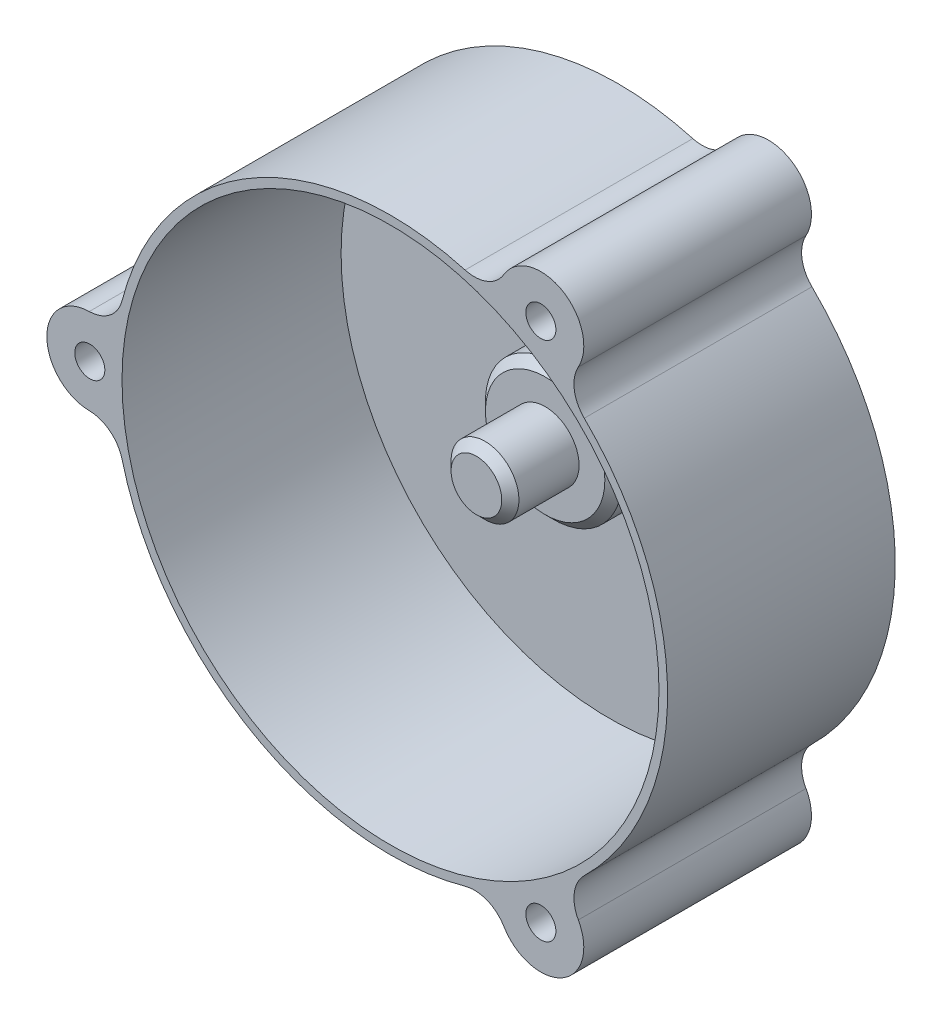
SolidWorks part; units mm, degrees
ref_plane "Front" through (0, 0, 0) normal (0, 0, 1) x (1, 0, 0)
ref_plane "Top" through (0, 0, 0) normal (0, 1, 0) x (1, 0, 0)
ref_plane "Right" through (0, 0, 0) normal (1, 0, 0) x (0, 0, -1)
sketch "Esquisse1" plane through (0, 0, 0) normal (0, 0, 1) x (1, 0, 0)
  circle A0 centre (0, 0) radius 31.25
  dimension "D1" = 62.5
extrude "Boss.-Extru.1" add sketch "Esquisse1" along normal blind 1
sketch "Esquisse2" plane through (0, 0, 1) normal (0, 0, 1) x (1, 0, 0)
  circle A0 centre (0, 0) radius 32.25
  circle A1 centre (0, 0) radius 31.25 construction
  circle A2 centre (0, 0) radius 31.25
  dimension "D1" = 1
extrude "Boss.-Extru.2" add sketch "Esquisse2" along normal blind 25.5 and the other way up to surface (1 mm away) other way up to face at (31.25, 0, 0)
sketch "Esquisse3" plane through (0, 0, 1) normal (0, 0, 1) x (1, 0, 0)
  circle A0 centre (0, 0) radius 7.95
  dimension "D1" = 15.9
extrude "Boss.-Extru.3" add sketch "Esquisse3" along normal blind 7.5
sketch "Esquisse4" plane through (0, 0, 8.5) normal (0, 0, 1) x (1, 0, 0)
  circle A0 centre (0, 0) radius 3.95
  dimension "D1" = 7.9
extrude "Boss.-Extru.4" add sketch "Esquisse4" along normal blind 8
chamfer "Chanfrein1" distance 1 angle 45 2 edges at (7.95, 0, 8.5) (3.95, 0, 16.5)
sketch "Esquisse5" plane through (0, 0, 26.5) normal (0, 0, 1) x (1, 0, 0)
  line L0 (-35, 0) -> (0, 0) construction
  arc A0 (-32.0009, -4.0007) -> (-32.0009, 4.0007) centre (-35, 0) cw
  circle A1 centre (0, 0) radius 32.25 construction
  arc A2 (-32.0009, 4.0007) -> (-32.0009, -4.0007) centre (0, 0) ccw
  dimension "D1" = 5
  dimension "D2" = 35
extrude "Boss.-Extru.5" add sketch "Esquisse5" against normal up to surface (26.5 mm away) up to face at (32.25, 0, 0)
sketch "Esquisse6" plane through (0, 0, 26.5) normal (0, 0, 1) x (1, 0, 0)
  circle A0 centre (-35, 0) radius 1.75
  dimension "D1" = 3.5
extrude "Enlèv. mat.-Extru.1" cut sketch "Esquisse6" against normal blind 10
fillet "Congé1" radius 4 2 edges at (-32.0009, 4.0007, 13.25) (-32.0009, -4.0007, 13.25)
pattern_circular "Répétition circulaire2" count 3 over 360 about axis through (0, 0, 26.5) along (0, 0, 1) of "Boss.-Extru.5", "Enlèv. mat.-Extru.1", "Congé1"
sketch "Esquisse7" plane through (0, 0, 26.5) normal (0, 0, 1) x (1, 0, 0)
  arc A12 (-35.064, 4.9996) -> (-35.064, -4.9996) centre (-35, 0) ccw
  arc A13 (-31.2404, -8.0062) -> (-35.064, -4.9996) centre (-35.1152, -8.9993) ccw
  arc A14 (-31.2404, -8.0062) -> (8.6866, -31.0581) centre (0, 0) ccw
  arc A15 (13.2022, -32.8661) -> (8.6866, -31.0581) centre (9.764, -34.9103) ccw
  arc A16 (13.2022, -32.8661) -> (21.8618, -27.8665) centre (17.5, -30.3109) ccw
  arc A17 (22.5538, -23.0519) -> (21.8618, -27.8665) centre (25.3512, -25.911) ccw
  arc A18 (22.5538, -23.0519) -> (22.5538, 23.0519) centre (0, 0) ccw
  arc A19 (21.8618, 27.8665) -> (22.5538, 23.0519) centre (25.3512, 25.911) ccw
  arc A20 (21.8618, 27.8665) -> (13.2022, 32.8661) centre (17.5, 30.3109) ccw
  arc A21 (8.6866, 31.0581) -> (13.2022, 32.8661) centre (9.764, 34.9103) ccw
  arc A22 (8.6866, 31.0581) -> (-31.2404, 8.0062) centre (0, 0) ccw
  arc A23 (-35.064, 4.9996) -> (-31.2404, 8.0062) centre (-35.1152, 8.9993) ccw
  arc A24 (-35.064, 4.9996) -> (-35.064, -4.9996) centre (-35, 0) ccw
  arc A25 (-31.2404, -8.0062) -> (-35.064, -4.9996) centre (-35.1152, -8.9993) ccw
  arc A26 (-31.2404, -8.0062) -> (8.6866, -31.0581) centre (0, 0) ccw
  arc A27 (13.2022, -32.8661) -> (8.6866, -31.0581) centre (9.764, -34.9103) ccw
  arc A28 (13.2022, -32.8661) -> (21.8618, -27.8665) centre (17.5, -30.3109) ccw
  arc A29 (22.5538, -23.0519) -> (21.8618, -27.8665) centre (25.3512, -25.911) ccw
  arc A30 (22.5538, -23.0519) -> (22.5538, 23.0519) centre (0, 0) ccw
  arc A31 (21.8618, 27.8665) -> (22.5538, 23.0519) centre (25.3512, 25.911) ccw
  arc A32 (21.8618, 27.8665) -> (13.2022, 32.8661) centre (17.5, 30.3109) ccw
  arc A33 (8.6866, 31.0581) -> (13.2022, 32.8661) centre (9.764, 34.9103) ccw
  arc A34 (8.6866, 31.0581) -> (-31.2404, 8.0062) centre (0, 0) ccw
  arc A35 (-35.064, 4.9996) -> (-31.2404, 8.0062) centre (-35.1152, 8.9993) ccw
  dimension "D1" = 0
extrude "Enlèv. mat.-Extru.2" [suppressed] cut sketch "Esquisse7" against normal blind 25.5
sketch "Esquisse8" plane through (0, 0, 1) normal (0, 0, 1) x (1, 0, 0)
  circle A0 centre (0, 0) radius 3.95
  dimension "D1" = 7.9
extrude "Boss.-Extru.6" [suppressed] add sketch "Esquisse8" along normal blind 8
sketch "Esquisse9" plane through (0, 0, 1) normal (0, 0, 1) x (1, 0, 0)
  circle A0 centre (-35, 0) radius 2.25
  circle A1 centre (17.5, 30.3109) radius 2.25
  circle A2 centre (17.5, -30.3109) radius 2.25
  dimension "D1" = 4.5
extrude "Enlèv. mat.-Extru.3" [suppressed] cut sketch "Esquisse9" against normal through all
chamfer "Chanfrein2" [suppressed] distance 1 angle 45
sketch "Esquisse10" plane through (0, 0, 1) normal (0, 0, 1) x (1, 0, 0)
  circle A0 centre (0, 0) radius 31
  circle A1 centre (0, 0) radius 27.25
  dimension "D1" = 62
  dimension "D2" = 54.5
extrude "Boss.-Extru.7" [suppressed] add sketch "Esquisse10" along normal blind 0.5
sketch "Esquisse11" [suppressed] plane through (0, 0, 1) normal (0, 0, 1) x (1, 0, 0)
  circle A12 centre (0, 0) radius 31 construction
  circle A13 centre (0, 0) radius 31
  arc A24 (-35.064, 4.9996) -> (-31.2404, 8.0062) centre (-35.1152, 8.9993) ccw
  arc A25 (-35.064, 4.9996) -> (-35.064, -4.9996) centre (-35, 0) ccw
  arc A26 (-31.2404, -8.0062) -> (-35.064, -4.9996) centre (-35.1152, -8.9993) ccw
  arc A27 (-31.2404, -8.0062) -> (8.6866, -31.0581) centre (0, 0) ccw
  arc A28 (13.2022, -32.8661) -> (8.6866, -31.0581) centre (9.764, -34.9103) ccw
  arc A29 (13.2022, -32.8661) -> (21.8618, -27.8665) centre (17.5, -30.3109) ccw
  arc A30 (22.5538, -23.0519) -> (21.8618, -27.8665) centre (25.3512, -25.911) ccw
  arc A31 (22.5538, -23.0519) -> (22.5538, 23.0519) centre (0, 0) ccw
  arc A32 (21.8618, 27.8665) -> (22.5538, 23.0519) centre (25.3512, 25.911) ccw
  arc A33 (21.8618, 27.8665) -> (13.2022, 32.8661) centre (17.5, 30.3109) ccw
  arc A34 (8.6866, 31.0581) -> (13.2022, 32.8661) centre (9.764, 34.9103) ccw
  arc A35 (8.6866, 31.0581) -> (-31.2404, 8.0062) centre (0, 0) ccw
  arc A36 (-35.064, 4.9996) -> (-31.2404, 8.0062) centre (-35.1152, 8.9993) ccw
  arc A37 (-35.064, 4.9996) -> (-35.064, -4.9996) centre (-35, 0) ccw
  arc A38 (-31.2404, -8.0062) -> (-35.064, -4.9996) centre (-35.1152, -8.9993) ccw
  arc A39 (-31.2404, -8.0062) -> (8.6866, -31.0581) centre (0, 0) ccw
  arc A40 (13.2022, -32.8661) -> (8.6866, -31.0581) centre (9.764, -34.9103) ccw
  arc A41 (13.2022, -32.8661) -> (21.8618, -27.8665) centre (17.5, -30.3109) ccw
  arc A42 (22.5538, -23.0519) -> (21.8618, -27.8665) centre (25.3512, -25.911) ccw
  arc A43 (22.5538, -23.0519) -> (22.5538, 23.0519) centre (0, 0) ccw
  arc A44 (21.8618, 27.8665) -> (22.5538, 23.0519) centre (25.3512, 25.911) ccw
  arc A45 (21.8618, 27.8665) -> (13.2022, 32.8661) centre (17.5, 30.3109) ccw
  arc A46 (8.6866, 31.0581) -> (13.2022, 32.8661) centre (9.764, 34.9103) ccw
  arc A47 (8.6866, 31.0581) -> (-31.2404, 8.0062) centre (0, 0) ccw
  dimension "D1" = 0
extrude "Enlèv. mat.-Extru.4" [suppressed] cut sketch "Esquisse11" against normal blind 0.5
sketch "Esquisse12" [suppressed] plane through (0, 0, 0) normal (0, 0, -1) x (-1, 0, 0)
  circle A0 centre (35, 0) radius 2.25 construction
  circle A1 centre (-17.5, -30.3109) radius 2.25 construction
  circle A2 centre (-17.5, 30.3109) radius 2.25 construction
  circle A3 centre (35, 0) radius 2.25
  circle A4 centre (-17.5, -30.3109) radius 2.25
  circle A5 centre (-17.5, 30.3109) radius 2.25
  arc A12 (35.064, -4.9996) -> (35.064, 4.9996) centre (35, 0) ccw
  arc A13 (31.2404, 8.0062) -> (35.064, 4.9996) centre (35.1152, 8.9993) ccw
  arc A14 (31.2404, 8.0062) -> (-8.6866, 31.0581) centre (0, 0) ccw
  arc A15 (-13.2022, 32.8661) -> (-8.6866, 31.0581) centre (-9.764, 34.9103) ccw
  arc A16 (-13.2022, 32.8661) -> (-21.8618, 27.8665) centre (-17.5, 30.3109) ccw
  arc A17 (-22.5538, 23.0519) -> (-21.8618, 27.8665) centre (-25.3512, 25.911) ccw
  arc A18 (-22.5538, 23.0519) -> (-22.5538, -23.0519) centre (0, 0) ccw
  arc A19 (-21.8618, -27.8665) -> (-22.5538, -23.0519) centre (-25.3512, -25.911) ccw
  arc A20 (-21.8618, -27.8665) -> (-13.2022, -32.8661) centre (-17.5, -30.3109) ccw
  arc A21 (-8.6866, -31.0581) -> (-13.2022, -32.8661) centre (-9.764, -34.9103) ccw
  arc A22 (-8.6866, -31.0581) -> (31.2404, -8.0062) centre (0, 0) ccw
  arc A23 (35.064, -4.9996) -> (31.2404, -8.0062) centre (35.1152, -8.9993) ccw
  arc A24 (35.064, -4.9996) -> (35.064, 4.9996) centre (35, 0) ccw
  arc A25 (31.2404, 8.0062) -> (35.064, 4.9996) centre (35.1152, 8.9993) ccw
  arc A26 (31.2404, 8.0062) -> (-8.6866, 31.0581) centre (0, 0) ccw
  arc A27 (-13.2022, 32.8661) -> (-8.6866, 31.0581) centre (-9.764, 34.9103) ccw
  arc A28 (-13.2022, 32.8661) -> (-21.8618, 27.8665) centre (-17.5, 30.3109) ccw
  arc A29 (-22.5538, 23.0519) -> (-21.8618, 27.8665) centre (-25.3512, 25.911) ccw
  arc A30 (-22.5538, 23.0519) -> (-22.5538, -23.0519) centre (0, 0) ccw
  arc A31 (-21.8618, -27.8665) -> (-22.5538, -23.0519) centre (-25.3512, -25.911) ccw
  arc A32 (-21.8618, -27.8665) -> (-13.2022, -32.8661) centre (-17.5, -30.3109) ccw
  arc A33 (-8.6866, -31.0581) -> (-13.2022, -32.8661) centre (-9.764, -34.9103) ccw
  arc A34 (-8.6866, -31.0581) -> (31.2404, -8.0062) centre (0, 0) ccw
  arc A35 (35.064, -4.9996) -> (31.2404, -8.0062) centre (35.1152, -8.9993) ccw
  point P0 (0, 0)
  dimension "D1" = 0
extrude "Boss.-Extru.8" [suppressed] add sketch "Esquisse12" along normal blind 1
sketch "Esquisse13" [suppressed] plane through (0, 0, 1.5) normal (0, 0, 1) x (1, 0, 0)
  line L0 (-14.5625, 25.223) -> (-13.625, 23.5992) construction
  line L1 (-14.5625, 25.223) -> (-15.5, 26.8468) construction
  line L2 (-35, 0) -> (-14.5625, 25.223) construction
  line L3 (-14.5625, 25.223) -> (17.5, 30.3109) construction
  line L4 (-13.625, 23.5992) -> (0, 0) construction
  line L5 (29.125, 0) -> (27.25, 0) construction
  line L6 (29.125, 0) -> (31, 0) construction
  line L7 (-14.5625, -25.223) -> (-13.625, -23.5992) construction
  line L8 (-14.5625, -25.223) -> (-15.5, -26.8468) construction
  circle A0 centre (-14.5625, 25.223) radius 1.25
  circle A1 centre (0, 0) radius 27.25 construction
  circle A2 centre (0, 0) radius 31 construction
  circle A3 centre (29.125, 0) radius 1.25
  circle A4 centre (-14.5625, -25.223) radius 1.25
  point P24 (0, 0)
  dimension "D1" = 2.5
  dimension "D2" = 3
extrude "Enlèv. mat.-Extru.5" [suppressed] cut sketch "Esquisse13" against normal through all
